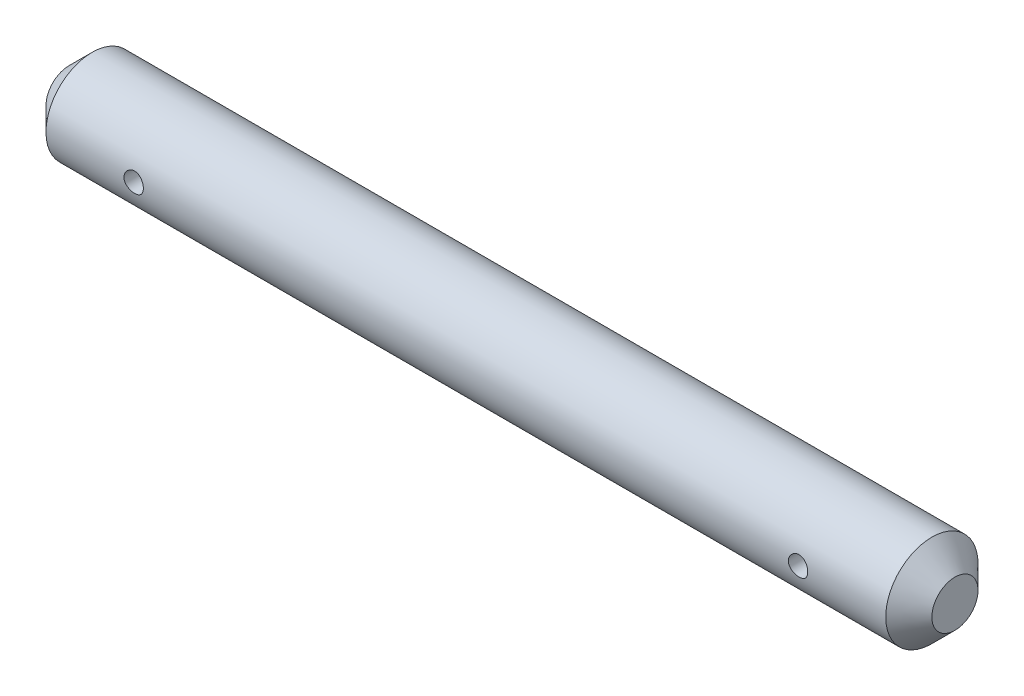
SolidWorks part; units mm, degrees
ref_plane "Front Plane" through (0, 0, 0) normal (0, 0, 1) x (1, 0, 0)
ref_plane "Top Plane" through (0, 0, 0) normal (0, 1, 0) x (1, 0, 0)
ref_plane "Right Plane" through (0, 0, 0) normal (1, 0, 0) x (0, 0, -1)
sketch "Sketch1" plane through (0, 0, 0) normal (0, 0, 1) x (1, 0, 0)
  line L0 (-48, 0) -> (48, 0) construction
  line L1 (-48, 5) -> (48, 5)
  line L2 (-48, 5) -> (-48, -5)
  line L3 (-48, -5) -> (48, -5)
  line L4 (48, 5) -> (48, -5)
  circle A0 centre (-36, 0) radius 1.05
  circle A1 centre (36, 0) radius 1.05
  dimension "D3" = 2.1
  dimension "D4" = 2.1
  dimension "D9" = 48
  dimension "D1" = 96
  dimension "D2" = 10
  dimension "D5" = 72
  dimension "D6" = 12
  dimension "D7" = 5
  dimension "D8" = 5
  dimension "D10" = 5
revolve "Revolve1" add sketch "Sketch1" angle 360 about L0 region at (0, 2.5149, 0) region at (36, 0.4456, 0) region at (-36, 0.4456, 0)
extrude "Cut-Extrude1" cut sketch "Sketch1<5>" against normal blind 20 and the other way blind 41 contours A0
sketch "Sketch1<5>" plane through (0, 0, 0) normal (0, 0, 1) x (1, 0, 0) same geometry as "Sketch1"
extrude "Cut-Extrude2" cut sketch "Sketch1<6>" against normal blind 20 and the other way blind 20 contours A1
sketch "Sketch1<6>" plane through (0, 0, 0) normal (0, 0, 1) x (1, 0, 0) same geometry as "Sketch1"
chamfer "Chamfer1" distance 2.5 angle 45 1 edges at (-48, -5, 0)
chamfer "Chamfer2" distance 2.5 angle 45 1 edges at (48, -5, 0)
